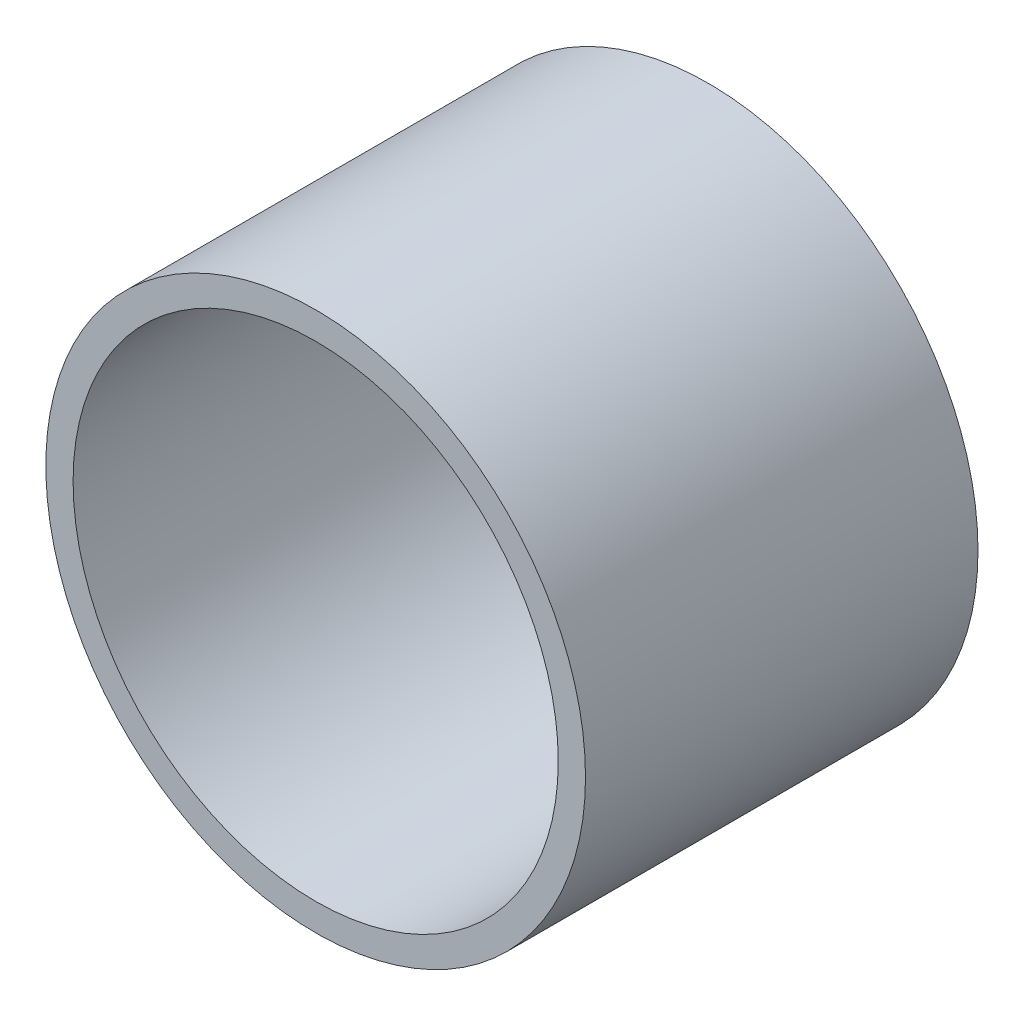
SolidWorks part; units mm, degrees
ref_plane "Front Plane" through (0, 0, 0) normal (0, 0, 1) x (1, 0, 0)
ref_plane "Top Plane" through (0, 0, 0) normal (0, 1, 0) x (1, 0, 0)
ref_plane "Right Plane" through (0, 0, 0) normal (1, 0, 0) x (0, 0, -1)
sketch "Sketch1" plane through (0, 0, 0) normal (0, 0, 1) x (1, 0, 0)
  circle A0 centre (0, 0) radius 25.146
  circle A1 centre (0, 0) radius 22.606
  dimension "D1" = 2.54
  dimension "D2" = 45.212
extrude "Boss-Extrude1" add sketch "Sketch1" along normal blind 36.576
